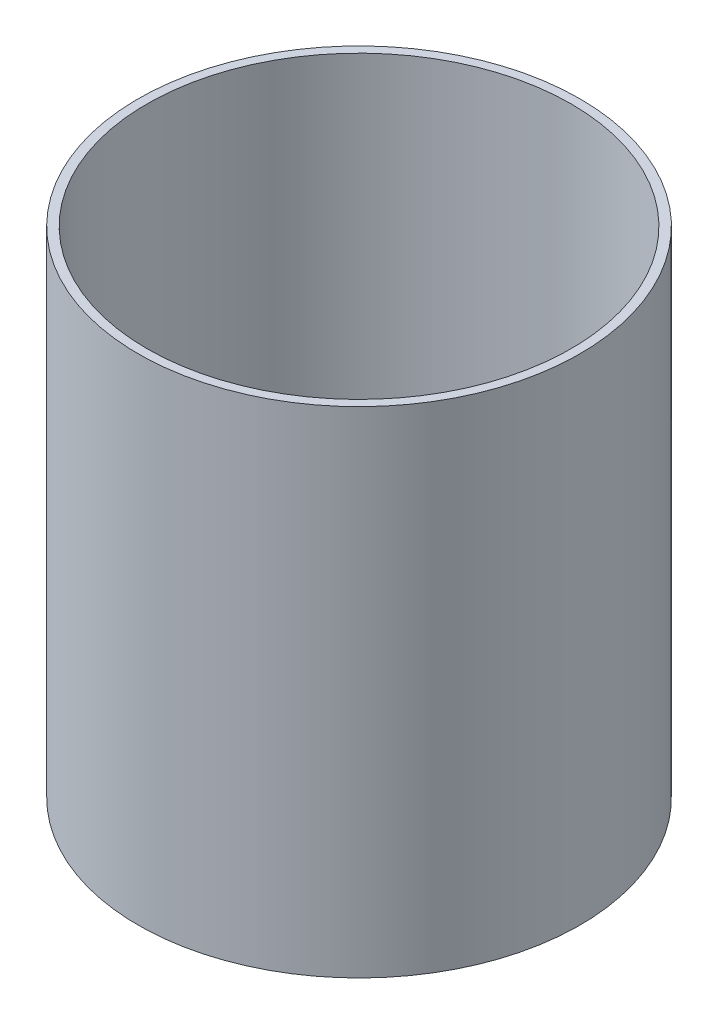
SolidWorks part; units mm, degrees
material "7075-T6 (SN)"
ref_plane "Front Plane" through (0, 0, 0) normal (0, 0, 1) x (1, 0, 0)
ref_plane "Top Plane" through (0, 0, 0) normal (0, 1, 0) x (1, 0, 0)
ref_plane "Right Plane" through (0, 0, 0) normal (1, 0, 0) x (0, 0, -1)
sketch "Sketch1" plane through (0, 0, 0) normal (0, 1, 0) x (1, 0, 0)
  circle A0 centre (0, 0) radius 1250
  circle A1 centre (0, 0) radius 1200
  circle A2 centre (0, 0) radius 1225 construction
  dimension "D1" = 2400
  dimension "D2" = 2500
  dimension "D3" = 2450
extrude "Boss-Extrude1" add sketch "Sketch1" along normal blind 2800
